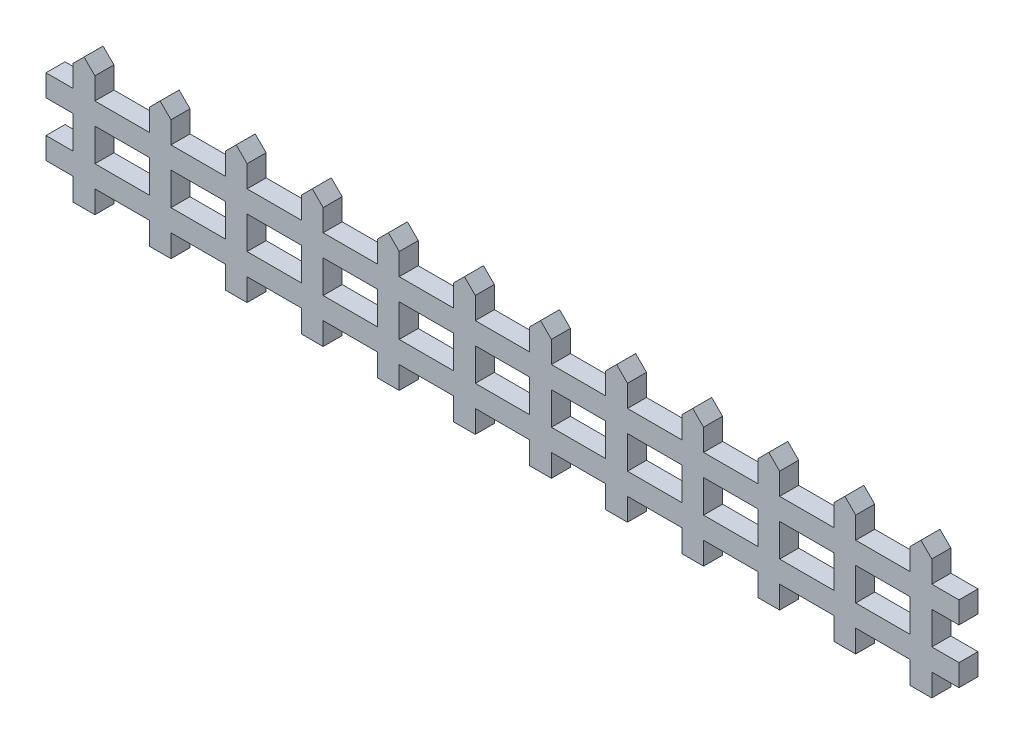
SolidWorks part; units mm, degrees
ref_plane "Front Plane" through (0, 0, 0) normal (1, 0, 0) x (0, 1, 0)
ref_plane "Top Plane" through (0, 0, 0) normal (0, 0, 1) x (0, 1, 0)
ref_plane "Right Plane" through (0, 0, 0) normal (0, 1, 0) x (-1, 0, 0)
sketch "Sketch1" plane through (0, 0, 0) normal (0, 0, 1) x (0, 1, 0)
  line L0 (-105, 74) -> (105, -74) construction
  line L1 (-105, 74) -> (105, 74) construction
  line L2 (-105, 74) -> (-105, -74) construction
  line L3 (-105, -74) -> (105, -74) construction
  line L4 (105, 74) -> (105, 63.1122) construction
  line L5 (84.9915, 53.1122) -> (82.9915, 53.1122)
  line L6 (100.9915, 67.1122) -> (98.9915, 67.1122)
  line L8 (100.9915, 63.1122) -> (98.9915, 63.1122)
  line L10 (94.9915, 72.1122) -> (98.9915, 72.1122)
  line L11 (94.9915, 72.1122) -> (94.9915, 67.1122)
  line L12 (94.9915, 44.1122) -> (98.9915, 44.1122)
  line L13 (98.9915, 72.1122) -> (98.9915, 67.1122)
  line L14 (88.9915, 72.1122) -> (84.9915, 72.1122)
  line L15 (88.9915, 72.1122) -> (88.9915, 67.1122)
  line L16 (88.9915, 44.1122) -> (84.9915, 44.1122)
  line L17 (84.9915, 72.1122) -> (84.9915, 67.1122)
  line L18 (100.9915, 53.1122) -> (98.9915, 53.1122)
  line L20 (100.9915, 49.1122) -> (98.9915, 49.1122)
  line L22 (84.9915, 49.1122) -> (82.9915, 49.1122)
  line L23 (88.9915, 49.1122) -> (88.9915, 44.1122)
  line L24 (98.9915, 49.1122) -> (98.9915, 44.1122)
  line L25 (94.9915, 49.1122) -> (94.9915, 44.1122)
  line L26 (84.9915, 49.1122) -> (84.9915, 44.1122)
  line L27 (94.9915, 53.1122) -> (88.9915, 53.1122)
  line L28 (94.9915, 63.1122) -> (88.9915, 63.1122)
  line L29 (94.9915, 63.1122) -> (94.9915, 53.1122)
  line L30 (98.9915, 63.1122) -> (98.9915, 53.1122)
  line L31 (88.9915, 63.1122) -> (88.9915, 53.1122)
  line L32 (84.9915, 63.1122) -> (84.9915, 53.1122)
  line L33 (84.9915, 63.1122) -> (82.9915, 63.1122)
  line L34 (84.9915, 67.1122) -> (82.9915, 67.1122)
  line L35 (94.9915, 67.1122) -> (88.9915, 67.1122)
  line L36 (94.9915, 49.1122) -> (88.9915, 49.1122)
  line L37 (105, 53.1122) -> (105, 49.1122)
  line L38 (100.9915, 67.1122) -> (105, 67.1122)
  line L40 (100.9915, 49.1122) -> (105, 49.1122)
  line L41 (105, 67.1122) -> (105, 63.1122)
  line L42 (82.9915, 67.1122) -> (80.8574, 67.1122)
  line L44 (82.9915, 49.1122) -> (80.8574, 49.1122)
  line L45 (80.8574, 67.1122) -> (80.8574, 63.1122)
  line L46 (82.9915, 63.1122) -> (80.8574, 63.1122)
  line L48 (82.9915, 53.1122) -> (80.8574, 53.1122)
  line L50 (100.9915, 53.1122) -> (105, 53.1122)
  line L52 (100.9915, 63.1122) -> (105, 63.1122)
  line L54 (105, 53.1122) -> (105, -74) construction
  line L56 (80.8574, 53.1122) -> (80.8574, 49.1122)
  dimension "D1" = 210
  dimension "D2" = 148
  dimension "D3" = 10
  dimension "D4" = 4
  dimension "D5" = 5
  dimension "D6" = 6
  dimension "D7" = 4
extrude "Boss-Extrude1" add sketch "Sketch1" along normal blind 3.5
chamfer "Chamfer1" distance 2 angle 45 4 edges at (-49.1122, 105, 1.75) (-53.1122, 105, 1.75) (-63.1122, 105, 1.75) (-67.1122, 105, 1.75)
pattern_linear "LPattern1" count 6 spacing 28 along (1, 0, 0) of "Chamfer1", "Boss-Extrude1"
